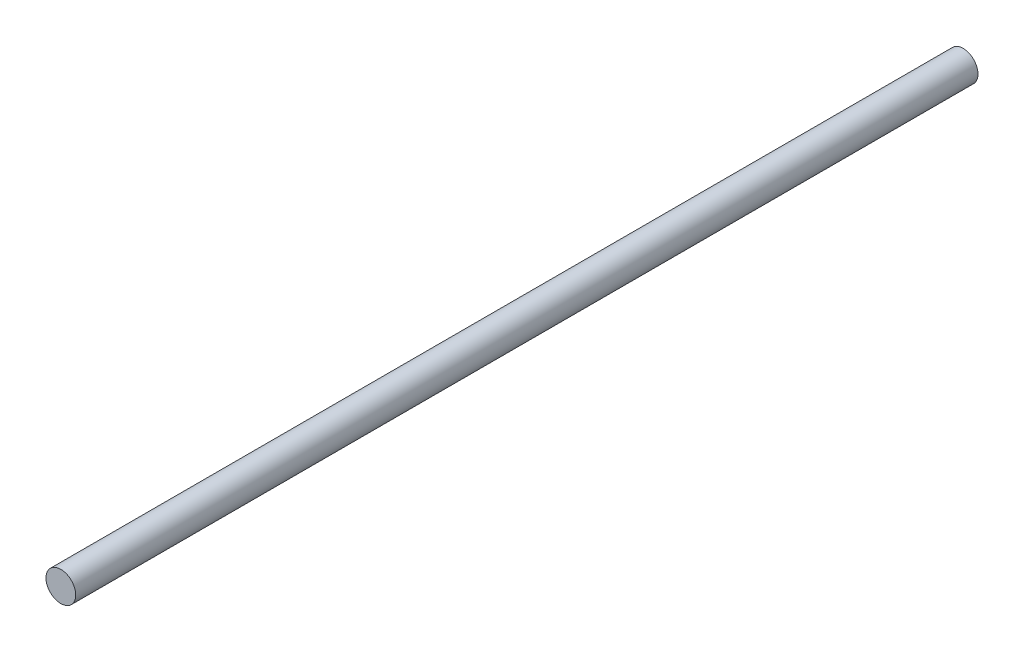
SolidWorks part; units mm, degrees
ref_plane "Ebene vorne" through (0, 0, 0) normal (0, 0, 1) x (1, 0, 0)
ref_plane "Ebene oben" through (0, 0, 0) normal (0, 1, 0) x (1, 0, 0)
ref_plane "Ebene rechts" through (0, 0, 0) normal (1, 0, 0) x (0, 0, -1)
sketch "Sketch1" plane through (0, 0, 0) normal (0, 0, 1) x (1, 0, 0)
  circle A0 centre (0, 0) radius 4
  dimension "D1" = 8
extrude "Boss-Extrude1" add sketch "Sketch1" along normal blind 243
